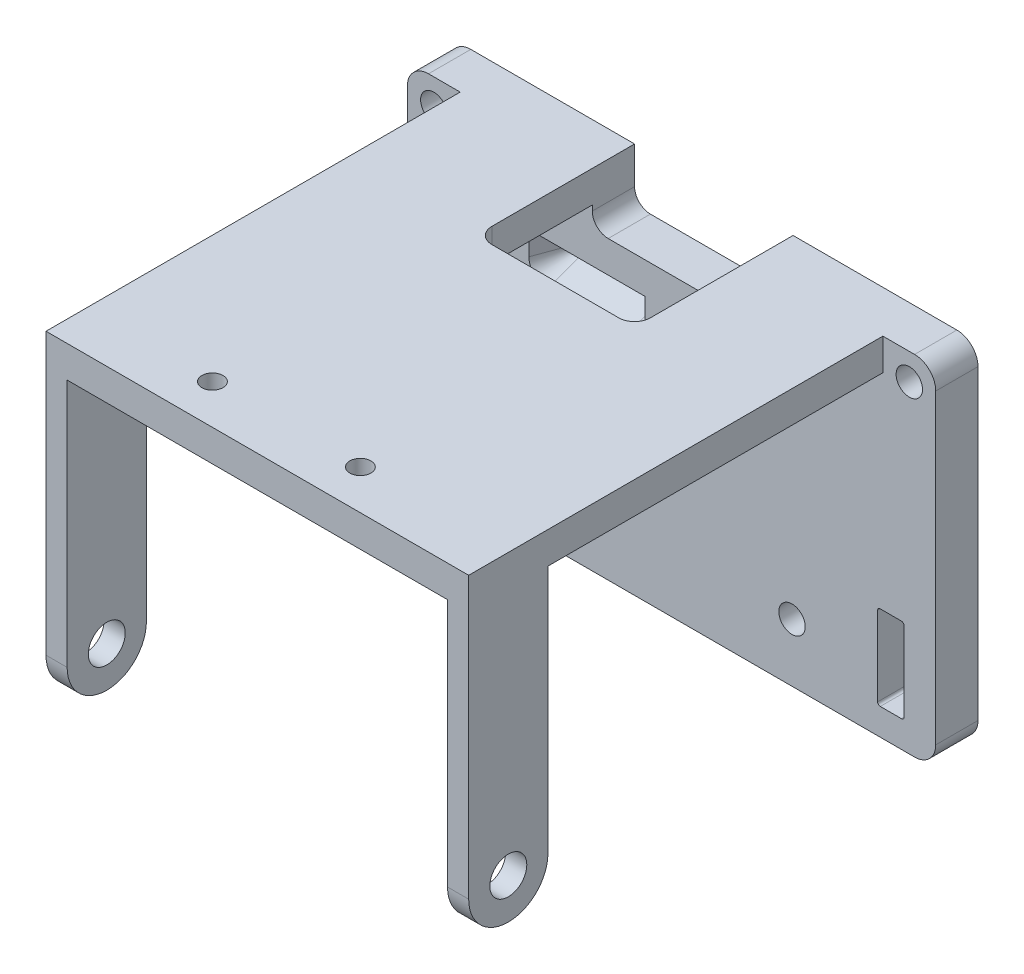
SolidWorks part; units mm, degrees
ref_plane "Front Plane" through (0, 0, 0) normal (0, 0, 1) x (1, 0, 0)
ref_plane "Top Plane" through (0, 0, 0) normal (0, 1, 0) x (1, 0, 0)
ref_plane "Right Plane" through (0, 0, 0) normal (1, 0, 0) x (0, 0, -1)
sketch "Sketch1" plane through (0, 0, 0) normal (0, 0, 1) x (1, 0, 0)
  line L1 (-20, -18) -> (20, -18)
  line L2 (-20, -18) -> (-20, 15)
  line L3 (-20, 15) -> (20, 15)
  line L4 (20, -18) -> (20, 15)
  line L5 (-20, -18) -> (20, 15) construction
  line L6 (-20, 15) -> (20, -18) construction
  point P0 (0, 0)
  dimension "D1" = 40
  dimension "D2" = 33
extrude "Boss-Extrude1" add sketch "Sketch1" along normal blind 4
sketch "Sketch3" plane through (0, 0, 4) normal (0, 0, 1) x (1, 0, 0)
  line L1 (-20, 12) -> (20, 12)
  line L2 (-20, 12) -> (-20, 15)
  line L3 (-20, 15) -> (20, 15)
  line L4 (20, 12) -> (20, 15)
  line L5 (-20, 12) -> (20, 15) construction
  line L6 (-20, 15) -> (20, 12) construction
  point P0 (0, 13.5)
  dimension "D1" = 40
  dimension "D2" = 3
extrude "Boss-Extrude2" add sketch "Sketch3" along normal blind 39.2
sketch "Sketch10" plane through (0, 12, 0) normal (0, -1, 0) x (1, 0, 0)
  line L1 (20, 43.2) -> (18, 43.2)
  line L2 (20, 43.2) -> (20, 35.7)
  line L3 (20, 35.7) -> (18, 35.7)
  line L4 (18, 43.2) -> (18, 35.7)
  dimension "D1" = 2
  dimension "D3" = 7.5
extrude "Boss-Extrude3" add sketch "Sketch10" along normal blind 27.3 from surface starting at face at (-5, 12, 33.4)
sketch "Sketch12" plane through (20, 0, 0) normal (1, 0, 0) x (0, 0, -1)
  line L0 (-4, -18) -> (-4, 12) construction
  line L1 (-4, 15) -> (0, 15)
  line L2 (-4, 15) -> (-4, -18)
  line L3 (-4, -18) -> (0, -18)
  line L4 (0, 15) -> (0, -18)
  dimension "D1" = 33
extrude "Boss-Extrude4" add sketch "Sketch12" along normal blind 5
sketch "Sketch13" plane through (0, 0, 4) normal (0, 0, 1) x (1, 0, 0)
  line L0 (22, -15.475) -> (19.5, -15.475)
  line L1 (22, -15.475) -> (22, -7.475)
  line L2 (19.5, -15.475) -> (19.5, -7.475)
  line L3 (22, -7.475) -> (19.5, -7.475)
  line L4 (22, -15.475) -> (19.5, -7.475) construction
  line L5 (19.5, -15.475) -> (22, -7.475) construction
  line L6 (-20, -18) -> (25, -18) construction
  line L7 (25, 15) -> (25, -18) construction
  dimension "D1" = 2.5
  dimension "D2" = 8
  dimension "D3" = 2.525
  dimension "D4" = 3
extrude "Cut-Extrude5" cut sketch "Sketch13" against normal through all
sketch "Sketch15" plane through (20, 0, 0) normal (1, 0, 0) x (0, 0, -1)
  line L0 (-43.2, -15.3) -> (-43.2, 12) construction
  line L1 (-35.7, -15.3) -> (-43.2, -15.3) construction
  circle A1 centre (-39.45, -11.475) radius 1.75
  dimension "D1" = 3.825
  dimension "D2" = 3.75
extrude "Cut-Extrude6" cut sketch "Sketch15" against normal up to next
fillet "Fillet6" radius 3.75 2 edges at (19, -15.3, 35.7) (19, -15.3, 43.2)
sketch "Sketch23" plane through (0, 0, 4) normal (0, 0, 1) x (1, 0, 0)
  line L1 (25, 15) -> (25, -18) construction
  line L2 (25, 15) -> (20, 15) construction
  circle A0 centre (11.4, -12.5) radius 1.25
  circle A1 centre (22.5, 12.5) radius 1.25
  dimension "D3" = 2.5
  dimension "D4" = 2.5
  dimension "D5" = 2.5
extrude "Cut-Extrude8" cut sketch "Sketch23" against normal up to next
fillet "Fillet8" radius 2 2 edges at (25, 15, 2) (25, -18, 2)
sketch "Sketch25" plane through (0, 12, 0) normal (0, -1, 0) x (1, 0, 0)
  line L1 (-1, 43.2) -> (-1, 4) construction
  circle A0 centre (6, 39.45) radius 1
  circle A1 centre (-8, 39.45) radius 1
extrude "Cut-Extrude10" cut sketch "Sketch25" against normal through all from surface starting at face at (2.6667, 12, 33.5417)
sketch "Sketch26" plane through (0, 0, 4) normal (0, 0, 1) x (1, 0, 0)
  line L1 (10, 7) -> (2, 7)
  line L2 (10, 7) -> (10, 4.5)
  line L3 (10, 4.5) -> (2, 4.5)
  line L4 (2, 7) -> (2, 4.5)
  line L5 (-20, 12) -> (20, 12) construction
  dimension "D1" = 8
  dimension "D2" = 2.5
  dimension "D3" = 7.5
extrude "Cut-Extrude11" cut sketch "Sketch26" against normal through all
fillet "Fillet3" radius 0.25 4 edges at (19.5, -15.475, 2) (22, -15.475, 2) (22, -7.475, 2) (19.5, -7.475, 2)
ref_plane "Plane1" through (0, 0, 0) normal (1, 0, 0) x (0, 0, -1)
mirror "Mirror10" about plane through (0, 0, 0) normal (1, 0, 0) of "Fillet6", "Boss-Extrude3", "Cut-Extrude6", "Boss-Extrude4", "Fillet8", "Cut-Extrude5", "Cut-Extrude8"
sketch "Sketch27" plane through (0, 12, 0) normal (0, -1, 0) x (-1, 0, 0)
  line L0 (8, -39.45) -> (8, -4) construction
  line L1 (23, -4) -> (-23, -4) construction
sketch "Sketch28" plane through (0, 0, 4) normal (0, 0, 1) x (1, 0, 0)
  line L1 (-12, 7) -> (-4, 7)
  line L2 (-12, 7) -> (-12, 4.5)
  line L3 (-12, 4.5) -> (-4, 4.5)
  line L4 (-4, 7) -> (-4, 4.5)
  line L5 (-20, 12) -> (20, 12) construction
  dimension "D1" = 8
  dimension "D2" = 4
  dimension "D3" = 2.5
  dimension "D4" = 7.5
extrude "Cut-Extrude12" cut sketch "Sketch28" against normal through all
fillet "Fillet9" radius 0.25 4 edges at (-4, 4.5, 2) (2, 4.5, 2) (10, 4.5, 2) (-12, 4.5, 2)
chamfer "Chamfer1" distance 1.5 angle 70 5 edges at (-12, 5.875, 4) (-4, 5.875, 4) (-11.9268, 4.5732, 4) (-4.0732, 4.5732, 4) (-8, 4.5, 4) first distance on face at (-8, 5.3994, 4)
chamfer "Chamfer2" distance 1.5 angle 81 5 edges at (2, 5.875, 0) (10, 5.875, 0) (2.0732, 4.5732, 0) (9.9268, 4.5732, 0) (6, 4.5, 0) first distance on face at (-8, 5.3817, 0)
sketch "Sketch29" plane through (0, 15, 0) normal (0, 1, 0) x (1, 0, 0)
  line L0 (23, 0) -> (-23, 0) construction
  line L1 (7.5, -15) -> (-7.5, -15)
  line L2 (7.5, -15) -> (7.5, 0)
  line L3 (7.5, 0) -> (-7.5, 0)
  line L4 (-7.5, -15) -> (-7.5, 0)
  line L5 (7.5, -15) -> (-7.5, 0) construction
  line L6 (7.5, 0) -> (-7.5, -15) construction
  point P0 (0, -7.5)
  dimension "D1" = 15
  dimension "D2" = 15
extrude "Cut-Extrude13" cut sketch "Sketch29" against normal blind 5
fillet "Fillet10" radius 1.5 4 edges at (7.5, 13.5, 15) (-7.5, 13.5, 15) (-7.5, 10, 2) (7.5, 10, 2)
